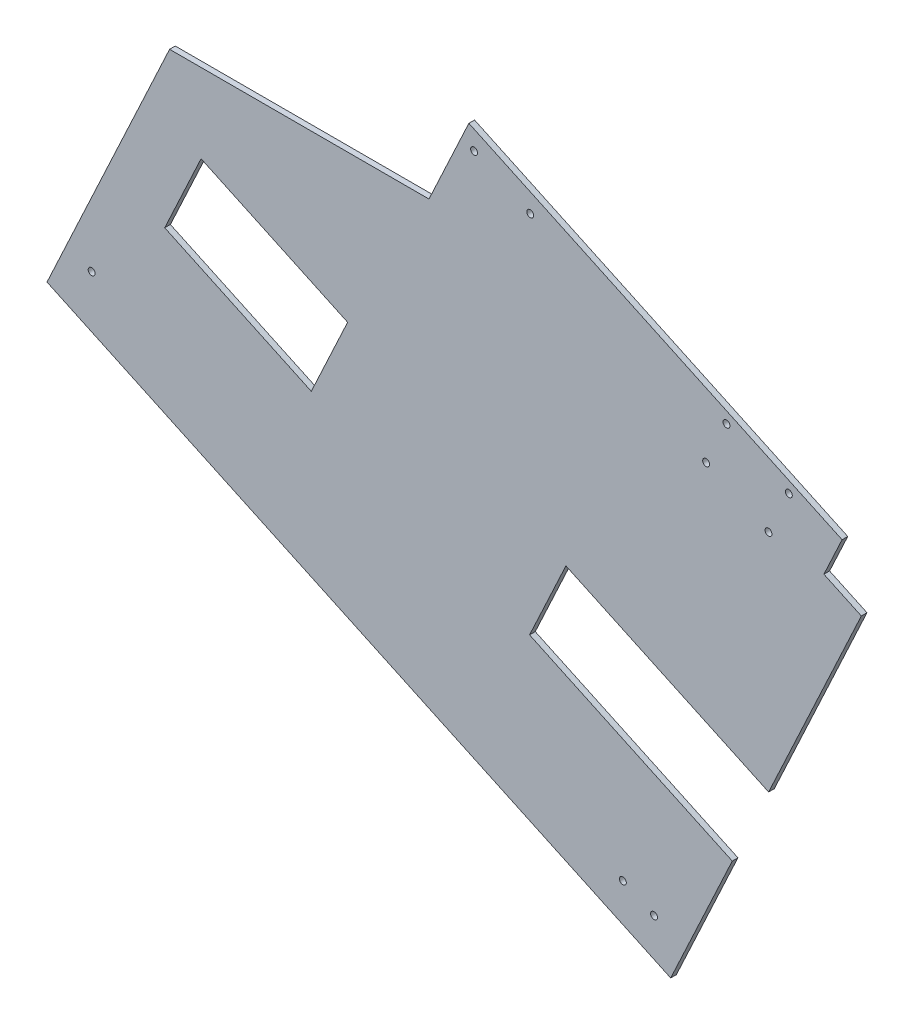
SolidWorks part; units mm, degrees
material "Balsa"
ref_plane "Front Plane" through (0, 0, 0) normal (0, 0, 1) x (1, 0, 0)
ref_plane "Top Plane" through (0, 0, 0) normal (0, 1, 0) x (1, 0, 0)
ref_plane "Right Plane" through (0, 0, 0) normal (1, 0, 0) x (0, 0, -1)
sketch "Sketch1" plane through (0, 0, 0) normal (0, 0, 1) x (1, 0, 0)
  line L0 (-261.1014, 0.0035) -> (-110.3324, 0.0035)
  line L1 (-110.3324, 0.0035) -> (-87.1479, 49.7228)
  line L2 (-87.1479, 49.7228) -> (129.7831, -51.4338)
  line L3 (129.7831, -51.4338) -> (119.2177, -74.0915)
  line L4 (119.2177, -74.0915) -> (140.969, -84.2344)
  line L5 (140.969, -84.2344) -> (30.1585, -321.8683)
  line L6 (30.1585, -321.8683) -> (-332.3646, -152.8209)
  line L7 (-332.3646, -152.8209) -> (-261.1014, 0.0035)
  line L8 (-257.4117, 0.0035) -> (-57.4117, 0.0035) construction
  line L9 (-332.3646, -152.8209) -> (-261.0998, 0.0069) construction
  line L10 (30.1585, -321.8683) -> (-332.3646, -152.8209) construction
  line L11 (140.969, -84.2344) -> (30.1585, -321.8683) construction
  line L12 (-189.2372, 97.3278) -> (129.7831, -51.4338) construction
  line L13 (119.2177, -74.0915) -> (140.969, -84.2344) construction
  line L14 (129.7831, -51.4338) -> (119.2177, -74.0915) construction
  line L15 (-110.3324, 0.0035) -> (-87.1479, 49.7228) construction
  circle A0 centre (87.0035, -69.0002) radius 2
  circle A1 centre (98.8369, -43.6236) radius 2
  circle A2 centre (62.5845, -26.7189) radius 2
  circle A3 centre (50.7512, -52.0955) radius 2
  circle A4 centre (2.3586, -286.8374) radius 2
  circle A5 centre (-306.4229, -134.5749) radius 2
  circle A6 centre (20.4847, -295.2897) radius 2
  circle A7 centre (2.3586, -286.8374) radius 2 construction
  circle A8 centre (20.4847, -295.2897) radius 2 construction
  dimension "D1" = 4
  dimension "D2" = 4
  dimension "D3" = 4
  dimension "D4" = 4
  dimension "D7" = 4
  dimension "D5" = 27.5
  dimension "D6" = 15.8
extrude "Boss-Extrude1" add sketch "Sketch1" along normal up to surface (3.3 mm away)
sketch "Sketch2" plane through (0, 0, 0) normal (0, 0, -1) x (-1, 0, 0)
  line L0 (87.1479, 49.7228) -> (110.3324, 0.0035) construction
  line L1 (-129.7831, -51.4338) -> (87.1479, 49.7228) construction
  circle A0 centre (51.4966, 22.0645) radius 2
  circle A1 centre (84.1237, 37.2788) radius 2
  dimension "D1" = 4
  dimension "D2" = 4
  dimension "D3" = 8
  dimension "D4" = 36
  dimension "D5" = 10
  dimension "D6" = 10
extrude "Cut-Extrude1" cut sketch "Sketch2" against normal through all
sketch "Sketch5" plane through (0, 0, 3.3) normal (0, 0, 1) x (1, 0, 0)
  line L0 (65.9543, -245.104) -> (-51.8657, -190.1636)
  line L1 (140.969, -84.2344) -> (30.1585, -321.8683) construction
  line L2 (-51.8657, -190.1636) -> (-30.7348, -144.8482)
  line L3 (-30.7348, -144.8482) -> (87.0852, -199.7886)
  line L4 (87.0852, -199.7886) -> (65.9543, -245.104)
  line L5 (119.2177, -74.0915) -> (140.969, -84.2344) construction
  dimension "D1" = 130
  dimension "D2" = 127.5
  dimension "D3" = 50
extrude "Cut-Extrude2" cut sketch "Sketch5" against normal blind 10
sketch "Sketch6" plane through (0, 0, 3.3) normal (0, 0, 1) x (1, 0, 0)
  line L0 (-178.7488, -130.9971) -> (-157.6179, -85.6817)
  line L1 (-157.6179, -85.6817) -> (-242.8108, -45.9555)
  line L2 (-242.8108, -45.9555) -> (-263.9417, -91.2709)
  line L3 (-263.9417, -91.2709) -> (-178.7488, -130.9971)
  line L5 (87.0852, -199.7886) -> (-30.7348, -144.8482) construction
  line L6 (-51.8657, -190.1636) -> (65.9543, -245.104) construction
  line L7 (-332.3646, -152.8209) -> (-261.1014, 0.0035) construction
  line L8 (129.7831, -51.4338) -> (119.2177, -74.0915) construction
  point P5 (0, 0)
  point P6 (-171.8509, -134.4855)
  point P7 (0, 0)
  dimension "D1" = 130
  dimension "D2" = 340
extrude "Cut-Extrude3" cut sketch "Sketch6" against normal blind 10
